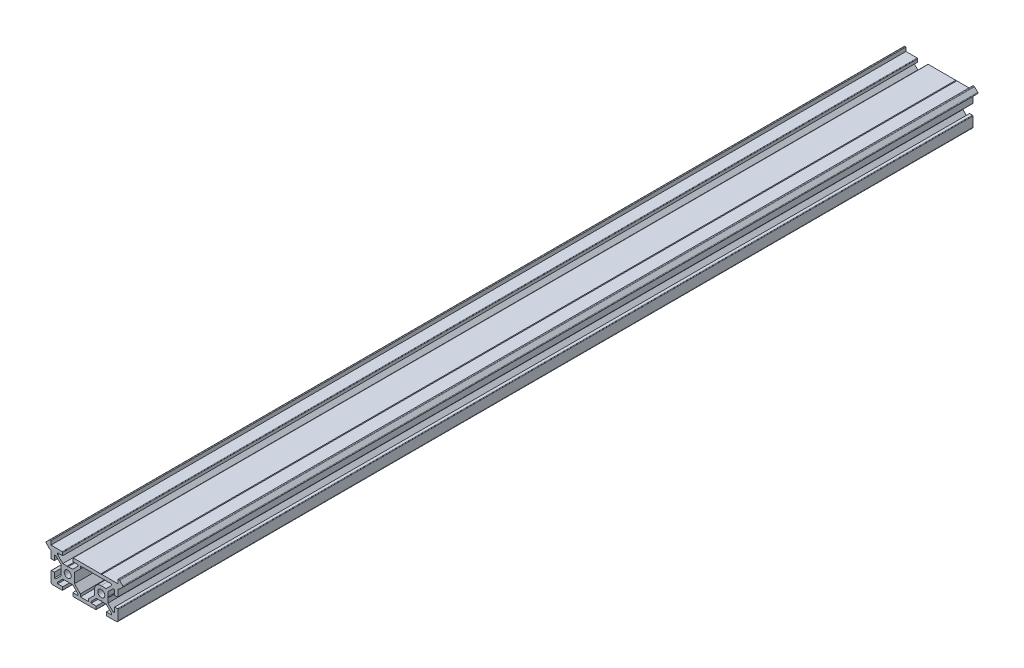
SolidWorks part; units mm, degrees
ref_plane "Front Plane" through (0, 0, 0) normal (0, 0, 1) x (1, 0, 0)
ref_plane "Top Plane" through (0, 0, 0) normal (0, 1, 0) x (1, 0, 0)
ref_plane "Right Plane" through (0, 0, 0) normal (1, 0, 0) x (0, 0, -1)
sketch "Model" plane through (0, 0, 0) normal (0, 0, 1) x (1, 0, 0)
  line L0 (0, 0) -> (0, 76.2) construction
  line L1 (0, 0) -> (101.6, 0) construction
  line L2 (0, 76.2) -> (101.6, 76.2) construction
  line L3 (101.6, 0) -> (101.6, 76.2) construction
  line L4 (28.7715, 48.1056) -> (30.6465, 49.9806)
  line L5 (31.5929, 50.127) -> (31.5929, 47.752)
  line L6 (31.5929, 44.877) -> (31.5929, 41.052)
  line L7 (31.5929, 34.452) -> (31.5929, 28.752)
  line L8 (33.5929, 31.752) -> (33.5929, 34.752)
  line L9 (33.5929, 40.752) -> (33.5929, 43.752)
  line L10 (35.5929, 29.752) -> (35.5929, 30.6914)
  line L11 (35.5929, 44.8127) -> (35.5929, 45.752)
  line L12 (37.5929, 40.6914) -> (37.5929, 38.052)
  line L13 (37.5929, 37.452) -> (37.5929, 34.8127)
  line L14 (38.5929, 28.052) -> (38.5929, 29.752)
  line L15 (38.5929, 45.752) -> (38.5929, 47.452)
  line L16 (32.5929, 27.752) -> (38.2929, 27.752)
  line L17 (44.8929, 27.752) -> (58.2929, 27.752)
  line L18 (64.8929, 27.752) -> (70.5929, 27.752)
  line L19 (37.5929, 38.052) -> (37.8929, 37.752)
  line L20 (41.5929, 34.052) -> (41.8929, 33.752)
  line L21 (30.6465, 45.5235) -> (28.7715, 47.3985)
  line L22 (41.8929, 41.752) -> (41.5929, 41.452)
  line L23 (37.8929, 37.752) -> (37.5929, 37.452)
  line L24 (67.5929, 29.752) -> (64.5929, 29.752)
  line L25 (58.5929, 29.752) -> (55.5929, 29.752)
  line L26 (54.0929, 29.752) -> (49.0929, 29.752)
  line L27 (47.5929, 29.752) -> (44.5929, 29.752)
  line L28 (38.5929, 29.752) -> (35.5929, 29.752)
  line L29 (34.5323, 43.752) -> (37.5929, 40.6914)
  line L30 (44.5323, 33.752) -> (47.5929, 30.6914)
  line L31 (44.5929, 47.452) -> (44.5929, 45.752)
  line L32 (44.5929, 29.752) -> (44.5929, 28.052)
  line L33 (47.5929, 44.8127) -> (44.5323, 41.752)
  line L34 (37.5929, 34.8127) -> (34.5323, 31.752)
  line L35 (69.5929, 31.752) -> (68.6536, 31.752)
  line L36 (34.5323, 31.752) -> (33.5929, 31.752)
  line L37 (49.0929, 31.3127) -> (45.5929, 34.8127)
  line L38 (38.6536, 41.752) -> (35.5929, 44.8127)
  line L39 (45.5929, 34.8127) -> (45.5929, 40.6914)
  line L40 (35.5929, 30.6914) -> (38.6536, 33.752)
  line L41 (45.5929, 40.6914) -> (49.0929, 44.1914)
  line L42 (38.6536, 33.752) -> (41.2929, 33.752)
  line L43 (41.8929, 33.752) -> (44.5323, 33.752)
  line L44 (58.6536, 33.752) -> (61.2929, 33.752)
  line L45 (61.8929, 33.752) -> (64.5323, 33.752)
  line L46 (41.5929, 41.452) -> (41.2929, 41.752)
  line L47 (47.5929, 45.752) -> (47.5929, 44.8127)
  line L48 (47.5929, 30.6914) -> (47.5929, 29.752)
  line L49 (41.2929, 33.752) -> (41.5929, 34.052)
  line L50 (71.2929, 34.752) -> (69.5929, 34.752)
  line L51 (33.5929, 34.752) -> (31.8929, 34.752)
  line L52 (49.0929, 29.752) -> (49.0929, 31.3127)
  line L53 (49.0929, 44.1914) -> (49.0929, 45.752)
  line L54 (61.5929, 47.452) -> (61.8929, 47.752)
  line L55 (31.8929, 40.752) -> (33.5929, 40.752)
  line L56 (69.5929, 40.752) -> (71.2929, 40.752)
  line L57 (54.0929, 31.3127) -> (54.0929, 29.752)
  line L58 (64.5323, 41.752) -> (61.4029, 41.752)
  line L59 (44.5323, 41.752) -> (41.8929, 41.752)
  line L60 (41.2929, 41.752) -> (38.6536, 41.752)
  line L61 (61.5929, 34.052) -> (61.8929, 33.752)
  line L62 (55.5929, 29.752) -> (55.5929, 30.6914)
  line L63 (33.5929, 43.752) -> (34.5323, 43.752)
  line L64 (68.6536, 43.752) -> (69.5929, 43.752)
  line L65 (57.5929, 37.942) -> (57.5929, 34.8127)
  line L66 (58.5929, 28.052) -> (58.5929, 29.752)
  line L67 (31.0929, 45.377) -> (31, 45.377)
  line L68 (72.0929, 45.377) -> (72.1858, 45.377)
  line L69 (35.5929, 45.752) -> (38.5929, 45.752)
  line L70 (44.5929, 45.752) -> (47.5929, 45.752)
  line L71 (49.0929, 45.752) -> (67.5929, 45.752)
  line L72 (64.5323, 33.752) -> (67.5929, 30.6914)
  line L73 (68.6536, 31.752) -> (65.5929, 34.8127)
  line L74 (67.5929, 44.8127) -> (64.5323, 41.752)
  line L75 (57.5929, 34.8127) -> (54.0929, 31.3127)
  line L76 (55.5929, 30.6914) -> (58.6536, 33.752)
  line L77 (65.5929, 40.6914) -> (68.6536, 43.752)
  line L78 (72.5394, 45.5235) -> (74.4144, 47.3985)
  line L79 (71.5929, 47.752) -> (61.8929, 47.752)
  line L80 (61.2929, 47.752) -> (44.8929, 47.752)
  line L81 (38.2929, 47.752) -> (31.5929, 47.752)
  line L82 (65.5929, 37.452) -> (65.2929, 37.752)
  line L83 (61.2929, 33.752) -> (61.5929, 34.052)
  line L84 (65.2929, 37.752) -> (65.5929, 38.052)
  line L85 (72.1858, 50.127) -> (71.5929, 50.127)
  line L86 (31, 50.127) -> (31.5929, 50.127)
  line L87 (64.5929, 29.752) -> (64.5929, 28.052)
  line L88 (61.2929, 47.752) -> (61.5929, 47.452)
  line L89 (65.5929, 34.8127) -> (65.5929, 37.452)
  line L90 (65.5929, 38.052) -> (65.5929, 40.6914)
  line L91 (67.5929, 45.752) -> (67.5929, 44.8127)
  line L92 (67.5929, 30.6914) -> (67.5929, 29.752)
  line L93 (69.5929, 43.752) -> (69.5929, 40.752)
  line L94 (69.5929, 34.752) -> (69.5929, 31.752)
  line L95 (71.5929, 50.127) -> (71.5929, 47.752)
  line L96 (71.5929, 28.752) -> (71.5929, 34.452)
  line L97 (71.5929, 41.052) -> (71.5929, 44.877)
  line L98 (74.4144, 48.1056) -> (72.5394, 49.9806)
  arc A0 (61.4029, 41.752) -> (57.5929, 37.942) centre (61.4029, 37.942) ccw
  circle A1 centre (61.5929, 37.752) radius 2.1
  circle A2 centre (41.5929, 37.752) radius 2.1
  arc A3 (31.5929, 28.752) -> (32.5929, 27.752) centre (32.5929, 28.752) ccw
  arc A4 (70.5929, 27.752) -> (71.5929, 28.752) centre (70.5929, 28.752) ccw
  arc A5 (31.5929, 44.877) -> (31.0929, 45.377) centre (31.0929, 44.877) ccw
  arc A6 (72.0929, 45.377) -> (71.5929, 44.877) centre (72.0929, 44.877) ccw
  arc A7 (31, 50.127) -> (30.6465, 49.9806) centre (31, 49.627) ccw
  arc A8 (28.7715, 48.1056) -> (28.7715, 47.3985) centre (29.125, 47.752) ccw
  arc A9 (30.6465, 45.5235) -> (31, 45.377) centre (31, 45.877) ccw
  arc A10 (72.5394, 49.9806) -> (72.1858, 50.127) centre (72.1858, 49.627) ccw
  arc A11 (74.4144, 47.3985) -> (74.4144, 48.1056) centre (74.0608, 47.752) ccw
  arc A12 (72.1858, 45.377) -> (72.5394, 45.5235) centre (72.1858, 45.877) ccw
  arc A13 (31.8929, 34.752) -> (31.5929, 34.452) centre (31.8929, 34.452) ccw
  arc A14 (44.8929, 47.752) -> (44.5929, 47.452) centre (44.8929, 47.452) ccw
  arc A15 (38.5929, 47.452) -> (38.2929, 47.752) centre (38.2929, 47.452) ccw
  arc A16 (31.5929, 41.052) -> (31.8929, 40.752) centre (31.8929, 41.052) ccw
  arc A17 (38.2929, 27.752) -> (38.5929, 28.052) centre (38.2929, 28.052) ccw
  arc A18 (44.5929, 28.052) -> (44.8929, 27.752) centre (44.8929, 28.052) ccw
  arc A19 (58.2929, 27.752) -> (58.5929, 28.052) centre (58.2929, 28.052) ccw
  arc A20 (64.5929, 28.052) -> (64.8929, 27.752) centre (64.8929, 28.052) ccw
  arc A21 (71.5929, 34.452) -> (71.2929, 34.752) centre (71.2929, 34.452) ccw
  arc A22 (71.2929, 40.752) -> (71.5929, 41.052) centre (71.2929, 41.052) ccw
extrude "Boss-Extrude1" add sketch "Model" against normal blind 510
ref_plane "Plane1" through (51.5929, 0, 0) normal (-1, 0, 0) x (0, 0, 1)
